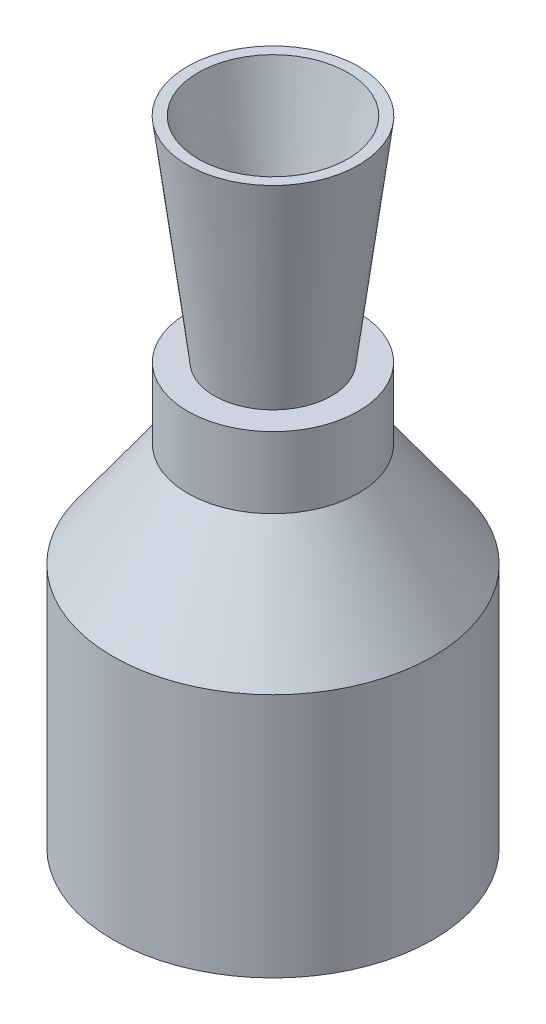
SolidWorks part; units mm, degrees
material "AISI 1045 Steel, cold drawn"
ref_plane "Front Plane" through (0, 0, 0) normal (0, 0, 1) x (1, 0, 0)
ref_plane "Top Plane" through (0, 0, 0) normal (0, 1, 0) x (1, 0, 0)
ref_plane "Right Plane" through (0, 0, 0) normal (1, 0, 0) x (0, 0, -1)
sketch "Sketch1" plane through (0, 0, 0) normal (0, 1, 0) x (1, 0, 0)
  circle A0 centre (0, 0) radius 22.5
  circle A1 centre (0, 0) radius 20.5
extrude "Boss-Extrude1" add sketch "Sketch1" along normal blind 34.5
sketch "Sketch5" plane through (0, 0, 0) normal (0, 0, 1) x (1, 0, 0)
  line L0 (22.5, 34.5) -> (12, 49.1202)
  line L1 (0, 0) -> (0, 50.7751) construction
  line L2 (12, 49.1202) -> (12, 59.1202)
  line L3 (20.5, 34.5) -> (3.5, 49.1202)
  line L4 (3.5, 49.1202) -> (3.5, 59.1202)
  line L5 (3.5, 59.1202) -> (12, 59.1202)
  line L6 (22.5, 34.5) -> (20.5, 34.5)
  dimension "D1" = 12
  dimension "D2" = 18
  dimension "D3" = 10
  dimension "D4" = 3.5
revolve "Revolve1" add sketch "Sketch5" angle 360 about L1
sketch "Sketch8" plane through (0, 59.1202, 0) normal (0, 1, 0) x (1, 0, 0)
  line L0 (0, 0) -> (12, 0) construction
  line L1 (0, 0) -> (0, 12) construction
ref_plane "Plane1" through (0, 0, 0) normal (0, 0, -1) x (-1, 0, 0)
sketch "Sketch10" plane through (0, 0, 0) normal (0, 0, -1) x (-1, 0, 0)
  line L0 (-3.5, 59.1202) -> (-10.5267, 89.1202)
  line L2 (-10.5267, 89.1202) -> (-12.0267, 89.1202)
  line L3 (-12.0267, 89.1202) -> (-8.25, 59.1202)
  line L4 (200000, 59.1202) -> (-200012, 59.1202) construction
  line L5 (0, 59.1202) -> (0, 74.0748) construction
  line L6 (-3.5, 59.1202) -> (-8.25, 59.1202)
  dimension "D1" = 8.25
  dimension "D2" = 30
  dimension "D3" = 1.5
revolve "Revolve3" add sketch "Sketch10" angle 360 about L5
